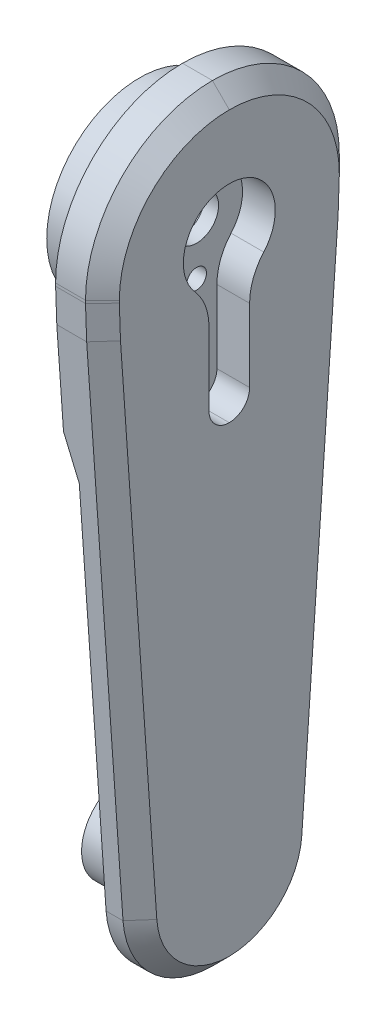
SolidWorks part; units mm, degrees
ref_plane "Front Plane" through (0, 0, 0) normal (0, 0, 1) x (1, 0, 0)
ref_plane "Top Plane" through (0, 0, 0) normal (0, 1, 0) x (1, 0, 0)
ref_plane "Right Plane" through (0, 0, 0) normal (1, 0, 0) x (0, 0, -1)
sketch "Sketch1" plane through (0, 0, 0) normal (1, 0, 0) x (0, 0, -1)
  line L1 (-10, 10) -> (10, 10)
  line L2 (-10, 10) -> (-10, -10)
  line L3 (-10, -10) -> (10, -10)
  line L4 (10, 10) -> (10, -10)
  line L5 (-10, 10) -> (10, -10) construction
  line L6 (-10, -10) -> (10, 10) construction
  point P0 (0, 0)
  dimension "D1" = 20
  dimension "D2" = 20
extrude "Boss-Extrude1" add sketch "Sketch1" along normal blind 20
sketch "Sketch2" plane through (20, 0, 0) normal (1, 0, 0) x (0, 0, -1)
  line L1 (-22.5, 35) -> (22.5, 35)
  line L2 (-22.5, 35) -> (-22.5, -35)
  line L3 (-22.5, -35) -> (22.5, -35)
  line L4 (22.5, 35) -> (22.5, -35)
  line L5 (-22.5, 35) -> (22.5, -35) construction
  line L6 (-22.5, -35) -> (22.5, 35) construction
  point P0 (0, 0)
  dimension "D1" = 45
  dimension "D2" = 70
extrude "Boss-Extrude2" add sketch "Sketch2" along normal blind 8.3
sketch "Sketch4" plane through (28.3, 0, 0) normal (1, 0, 0) x (0, 0, -1)
  line L0 (0, 7.65) -> (0, 8.1702) construction
  line L1 (7.65, 7.65) -> (-7.65, 7.65) construction
  line L17 (3.6, -26.55) -> (-3.6, -26.55) construction
  line L18 (-7.65, 7.65) -> (7.65, 7.65) construction
  line L22 (-7.65, 7.65) -> (-7.65, -27.55) construction
  line L23 (-7.65, -27.55) -> (7.65, -27.55) construction
  line L24 (7.65, 7.65) -> (7.65, -27.55) construction
  line L25 (-7.65, 7.65) -> (7.65, -27.55) construction
  line L26 (-7.65, -27.55) -> (7.65, 7.65) construction
  line L27 (3.6, -26.55) -> (3.6, -28.55) construction
  line L28 (3.6, -28.55) -> (-3.6, -28.55) construction
  line L29 (-3.6, -26.55) -> (-3.6, -28.55) construction
  line L30 (3.6, -26.55) -> (-3.6, -28.55) construction
  line L31 (3.6, -28.55) -> (-3.6, -26.55) construction
  line L34 (3.6, -28.55) -> (-3.6, -28.55)
  line L35 (-3.6, -28.55) -> (-3.6, -7.3118)
  line L36 (3.6, -28.55) -> (3.6, -7.3118)
  arc A1 (3.6, -6.75) -> (-3.6, -6.75) centre (0, 0) ccw construction
  arc A2 (3.6, -7.3118) -> (-3.6, -7.3118) centre (0, 0) ccw
  point P1 (0, -27.55)
  point P7 (0, -13.75)
  point P10 (0, 7.65)
  point P14 (0, -9.95)
  dimension "D1" = 15.3
  dimension "D5" = 2
  dimension "D2" = 15.3
  dimension "D3" = 35.2
  dimension "D4" = 7.2
extrude "Cut-Extrude1" cut sketch "Sketch4" against normal blind 5.8
fillet "Fillet1" radius 3.6 2 edges at (25.4, -28.55, 3.6) (25.4, -28.55, -3.6)
fillet "Fillet2" radius 10 2 edges at (25.4, -7.3118, 3.6) (25.4, -7.3118, -3.6)
sketch "Sketch5" plane through (0, 0, 0) normal (-1, 0, 0) x (0, 0, 1)
  circle A0 centre (0, 0) radius 3.9
  dimension "D1" = 7.8
extrude "Cut-Extrude2" cut sketch "Sketch5" against normal through all
sketch "Sketch6" plane through (22.5, 0, 0) normal (1, 0, 0) x (0, 0, -1)
  line L0 (0, -19.35) -> (0, 0) construction
  line L1 (0, -25.65) -> (0, -23.15) construction
  line L2 (0, -23.15) -> (0, -21.85) construction
  line L3 (0, -21.85) -> (0, -19.35) construction
  line L5 (0, 0) -> (1.164, 0) construction
  line L6 (0, 0) -> (0, -9.35) construction
  line L7 (0, -9.35) -> (1.164, -9.35) construction
  line L8 (1.164, 0) -> (1.164, -9.35) construction
  line L9 (0, 0) -> (1.164, -9.35) construction
  line L10 (0, -9.35) -> (1.164, 0) construction
  circle A0 centre (0, -20.6) radius 1.75
  circle A1 centre (0, -9.35) radius 1.75
  point P11 (0.582, -4.675)
  dimension "D5" = 3.5
  dimension "D6" = 9.35
  dimension "D7" = 3.5
  dimension "D1" = 19.35
  dimension "D2" = 2.5
  dimension "D3" = 1.3
  dimension "D4" = 2.5
extrude "Cut-Extrude3" cut sketch "Sketch6" against normal up to next
sketch "Sketch13" plane through (0, 0, 0) normal (-1, 0, 0) x (0, 0, 1)
  line L1 (-10, 10) -> (10, 10)
  line L2 (-10, 10) -> (-10, -10)
  line L3 (-10, -10) -> (10, -10)
  line L4 (10, 10) -> (10, -10)
extrude "Cut-Extrude9" cut sketch "Sketch13" against normal up to surface (20 mm away) up to face at (20, -20.6, -1.75)
sketch "Sketch14" plane through (20, 0, 0) normal (-1, 0, 0) x (0, 0, 1)
  line L0 (0, -11.1) -> (0, -18.85) construction
  circle A0 centre (0, -9.35) radius 1.75 construction
  circle A1 centre (0, -20.6) radius 1.75 construction
  circle A3 centre (0, 0) radius 16.475
  circle A4 centre (0, 0) radius 3.9 construction
  point P7 (0, -14.975)
  dimension "D1" = 32.95
  dimension "D2" = 12.575
extrude "Boss-Extrude3" add sketch "Sketch14" along normal blind 7.6 contours A3
sketch "Sketch15" plane through (0, 35, 0) normal (0, 1, 0) x (1, 0, 0)
  line L1 (20, 22.5) -> (28.3, 22.5)
  line L2 (20, 22.5) -> (20, -22.5)
  line L3 (20, -22.5) -> (28.3, -22.5)
  line L4 (28.3, 22.5) -> (28.3, -22.5)
extrude "Cut-Extrude10" cut sketch "Sketch15" against normal blind 12.5
sketch "Sketch16" plane through (12.4, 0, 0) normal (-1, 0, 0) x (0, 0, 1)
  circle A4 centre (0, 0) radius 13.475
  circle A5 centre (0, 0) radius 13.475
  dimension "D1" = 3
extrude "Cut-Extrude11" cut sketch "Sketch16" against normal blind 7.6
sketch "Sketch17" plane through (20, 0, 0) normal (-1, 0, 0) x (0, 0, 1)
  line L0 (0, 0) -> (-22.5, 0) construction
  line L1 (-22.5, -35) -> (-22.5, 22.5) construction
  line L2 (0, 0) -> (22.5, 0) construction
  line L3 (22.5, 22.5) -> (22.5, -35) construction
  line L4 (0, 0) -> (0, 22.5) construction
  line L5 (-22.5, 22.5) -> (22.5, 22.5) construction
sketch "Sketch18" plane through (0, -35, 0) normal (0, -1, 0) x (1, 0, 0)
  line L0 (20, 0) -> (20, 22.5) construction
  line L1 (20, 22.5) -> (28.3, 22.5)
  line L2 (20, 22.5) -> (20, -22.5)
  line L3 (20, -22.5) -> (28.3, -22.5)
  line L4 (28.3, 22.5) -> (28.3, -22.5)
  line L5 (28.3, 22.5) -> (20, 22.5) construction
  line L6 (28.3, 22.5) -> (28.3, -22.5) construction
extrude "Boss-Extrude4" add sketch "Sketch18" along normal blind 78.5
sketch "Sketch20" plane through (20, 0, 0) normal (-1, 0, 0) x (0, 0, 1)
  line L0 (0, 0) -> (0, -100) construction
  line L1 (22.5, 22.5) -> (22.5, -113.5) construction
  line L2 (-22.5, -113.5) -> (22.5, -113.5)
  line L3 (-22.5, -113.5) -> (-22.5, -33.5)
  line L4 (-22.5, -33.5) -> (22.5, -33.5)
  line L5 (22.5, -113.5) -> (22.5, -33.5)
  dimension "D1" = 100
  dimension "D2" = 80
fillet "Fillet5" radius 22.5 2 edges at (24.15, 22.5, -22.5) (24.15, 22.5, 22.5)
extrude "Cut-Extrude12" cut sketch "Sketch20" against normal blind 2.3
sketch "Sketch21" plane through (22.3, 0, 0) normal (-1, 0, 0) x (0, 0, 1)
  line L0 (0, -113.5) -> (0, -99.5) construction
  line L1 (-22.5, -113.5) -> (22.5, -113.5) construction
  circle A0 centre (0, -99.5) radius 8
  dimension "D2" = 16
  dimension "D1" = 14
extrude "Boss-Extrude5" add sketch "Sketch21" along normal blind 12.2
chamfer "Chamfer1" distance 10 angle 18 1 edges at (20, -33.5, 0) first distance on face at (20, -20.6, -1.75)
chamfer "Chamfer2" distance 110 angle 4 2 edges at (25.3, -113.5, -22.5) (25.3, -113.5, 22.5) first distance on face at (23.5333, -46.8464, -22.5) first distance on face at (23.5333, -46.8464, 22.5)
chamfer "Chamfer3" distance 3 angle 2 2 edges at (24.15, -3.5, 22.5) (24.15, -3.5, -22.5) first distance on face at (23.5333, -48.0131, 19.3873) first distance on face at (23.5333, -48.0131, -19.3873)
fillet "Fillet6" radius 16 2 edges at (25.3, -113.5, -14.8081) (25.3, -113.5, 14.8081)
chamfer "Chamfer4" distance 3 angle 45 10 edges at (28.3, -3.4963, -22.3954) (28.3, -0.25, -22.5) (28.3, 15.9099, -15.9099) (28.3, 15.9099, 15.9099) (28.3, -0.25, 22.5) (28.3, -3.4963, 22.3954) (28.3, -52.5544, 19.0698) (28.3, -109.1633, 10.8407) (28.3, -109.1633, -10.8407) (28.3, -52.5544, -19.0698)
sketch "Sketch23" plane through (10.1, 0, 0) normal (-1, 0, 0) x (0, 0, 1)
  line L0 (0, -99.5) -> (-8, -99.5) construction
  line L1 (0, -99.5) -> (8, -99.5) construction
  line L2 (-6.35, -99.5) -> (-8, -99.5)
  circle A0 centre (0, -99.5) radius 8 construction
  circle A1 centre (-4, -99.5) radius 2.35
  circle A2 centre (4, -99.5) radius 2.35
  point P0 (0, -99.5)
  dimension "D1" = 4.7
  dimension "D2" = 4.7
extrude "Cut-Extrude13" cut sketch "Sketch23" against normal blind 8 contours A2 | A1
chamfer "Chamfer5" distance 1 angle 45 2 edges at (10.1, -99.5, 6.35) (10.1, -99.5, -1.65)
sketch "Sketch24" plane through (20, 0, 0) normal (-1, 0, 0) x (0, 0, 1)
  line L0 (0, 0) -> (0, 13.475) construction
  line L1 (-16.475, 0) -> (-5.975, 0) construction
  line L3 (3.9, 0) -> (16.475, 0) construction
  circle A0 centre (0, 0) radius 3.9 construction
  circle A4 centre (0, 0) radius 16.475 construction
  circle A5 centre (-11.225, 0) radius 5
  circle A6 centre (0, 0) radius 13.475 construction
  circle A7 centre (11.225, 0) radius 5
  dimension "D1" = 10.5
  dimension "D2" = 10
extrude "Boss-Extrude6" add sketch "Sketch24" along normal up to surface (7.6 mm away) up to face at (12.4, 0, 13.475)
fillet "Fillet8" radius 2 4 edges at (16.2, 4.8109, -12.5869) (16.2, -4.8109, -12.5869) (16.2, -4.8109, 12.5869) (16.2, 4.8109, 12.5869)
fillet "Fillet9" radius 1.5 8 edges at (20, 6.076, 11.1856) (20, 0, 6.225) (20, -6.076, 11.1856) (20, -13.475, 0) (20, -6.076, -11.1856) (20, 0, -6.225) (20, 6.076, -11.1856) (20, 13.475, 0)
sketch "Sketch27" plane through (12.4, 0, 0) normal (-1, 0, 0) x (0, 0, 1)
  line L0 (-16.475, 0) -> (-5.975, 0) construction
  line L1 (0, 0) -> (-22.5, 0) construction
  line L2 (0, 0) -> (0, 5.9787) construction
  line L3 (0, 0) -> (0, 22.5) construction
  circle A0 centre (0, 0) radius 16.475 construction
  circle A1 centre (-11.225, 0) radius 2.35
  circle A2 centre (11.225, 0) radius 2.35
  dimension "D2" = 4.7
  dimension "D1" = 10.5
extrude "Cut-Extrude14" cut sketch "Sketch27" against normal blind 8 contours A1 | A2
chamfer "Chamfer6" distance 1 angle 45 2 edges at (12.4, 0, -8.875) (12.4, 0, 8.875)
